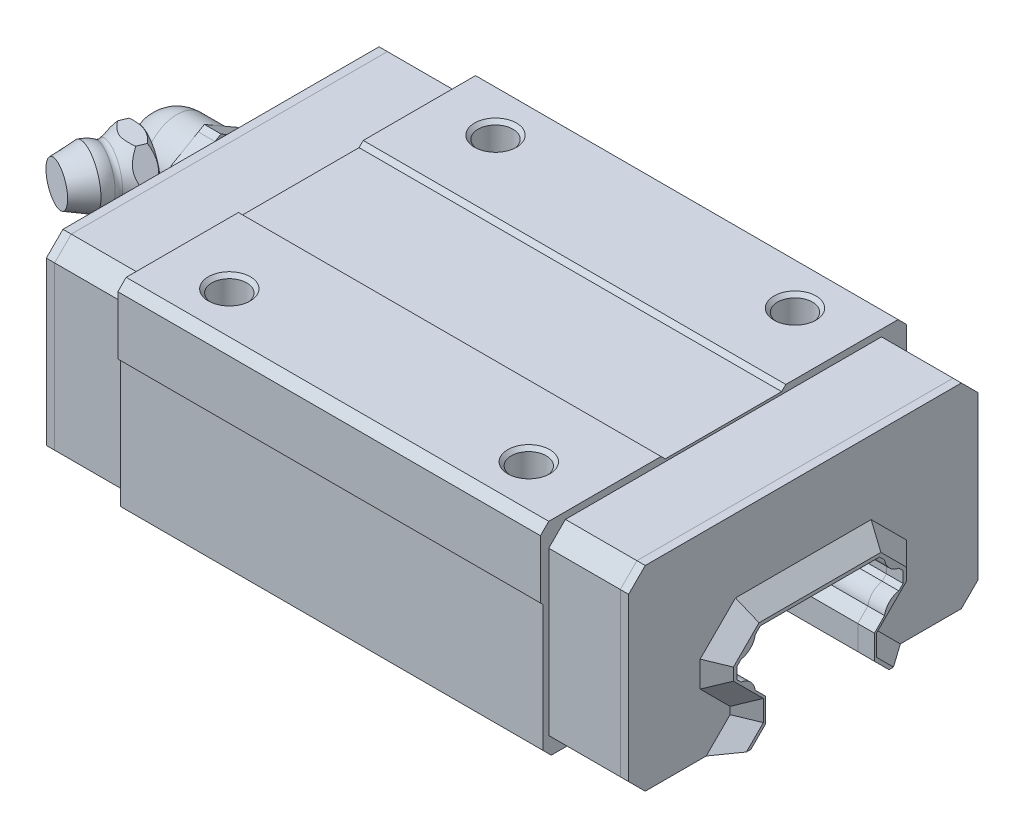
SolidWorks part; units mm, degrees
ref_plane "Front Plane" through (0, 0, 0) normal (0, 0, 1) x (1, 0, 0)
ref_plane "Top Plane" through (0, 0, 0) normal (0, 1, 0) x (1, 0, 0)
ref_plane "Right Plane" through (0, 0, 0) normal (1, 0, 0) x (0, 0, -1)
sketch "Sketch6" plane through (0, 48.7499, 0) normal (0, 1, 0) x (-1, 0, 0)
  line L0 (-67, -46.0009) -> (-233, -46.0009) construction
  line L1 (-124.6001, -68.0009) -> (-124.6001, -24.0009)
  line L2 (-175.4001, -68.0009) -> (-175.4001, -24.0009)
  line L3 (-70, -56.0009) -> (-70, -36.0009)
  line L4 (-116.0002, -67.0009) -> (-116.0002, -25.0009)
  line L5 (-115.0002, -67.0009) -> (-115.0002, -25.0009)
  line L6 (-113.0002, -56.4008) -> (-113.0002, -35.601)
  line L7 (-115.0002, -67.0009) -> (-124.6001, -67.0009)
  line L8 (-113.0002, -56.4008) -> (-115.0002, -58.4008)
  line L9 (-70, -56.0009) -> (-113.0002, -56.0009)
  line L10 (-70, -53.1609) -> (-113.0002, -53.1609)
  line L11 (-113.0002, -35.601) -> (-115.0002, -33.601)
  line L12 (-115.0002, -25.0009) -> (-124.6001, -25.0009)
  line L13 (-70, -38.841) -> (-103.6509, -38.841)
  line L14 (-70, -36.0009) -> (-104.6381, -36.0009)
  line L15 (-230, -56.0009) -> (-230, -36.0009)
  line L16 (-230, -36.0009) -> (-187, -36.0009)
  line L17 (-184, -67.0009) -> (-184, -25.0009)
  line L18 (-185, -67.0009) -> (-185, -25.0009)
  line L19 (-187, -56.4008) -> (-187, -35.601)
  line L20 (-185, -67.0009) -> (-175.4001, -67.0009)
  line L21 (-187, -56.4008) -> (-185, -58.4008)
  line L22 (-230, -56.0009) -> (-187, -56.0009)
  line L23 (-230.0002, -53.1609) -> (-187, -53.1609)
  line L24 (-187, -35.601) -> (-185, -33.601)
  line L25 (-185, -25.0009) -> (-175.4001, -25.0009)
  line L26 (-230.0002, -38.841) -> (-187, -38.841)
  line L27 (-210, -52.0009) -> (-210, -40.0009) construction
  line L28 (-90, -52.0009) -> (-90, -40.0009) construction
  line L29 (-150, -52.0009) -> (-150, -40.0009) construction
  line L30 (-182.2712, -57.0009) -> (-187.2456, -57.0009) construction
  line L31 (-182.2712, -35.0009) -> (-187.2456, -35.0009) construction
  line L32 (-117.7288, -57.0009) -> (-112.7544, -57.0009) construction
  line L33 (-117.7288, -35.0009) -> (-112.7544, -35.0009) construction
  line L34 (-113.0003, -42.0009) -> (-113.0003, -50.0009)
  line L35 (-109.7003, -50.0009) -> (-113.0003, -50.0009)
  line L36 (-111.3204, -42.0009) -> (-113.0003, -42.0009)
  line L37 (-105.7003, -46.0009) -> (-105.7003, -44.3288)
  line L38 (-113.0003, -50.0009) -> (-115.0002, -50.0009)
  line L39 (-113.0003, -42.0009) -> (-115.0002, -42.0009)
  line L40 (-103.483, -36.4794) -> (-107.9177, -34.6425)
  line L41 (-103.6848, -39.3183) -> (-109.7824, -36.7926)
  line L42 (-103.483, -36.4794) -> (-103.6848, -39.3183)
  line L43 (-107.9177, -34.6425) -> (-109.7824, -36.7926)
  line L44 (-104.4235, -43.0391) -> (-104.8382, -44.0402)
  line L45 (-111.8911, -39.946) -> (-112.3058, -40.947)
  line L46 (-105.6176, -44.363) -> (-104.8382, -44.0402)
  line L47 (-106.0608, -41.7115) -> (-106.9334, -43.8181)
  line L48 (-109.7946, -40.1649) -> (-110.6671, -42.2715)
  line L49 (-105.6176, -44.363) -> (-111.9829, -41.7265)
  line L50 (-112.3058, -40.947) -> (-111.9829, -41.7265)
  line L51 (-104.6533, -42.2945) -> (-111.2021, -39.5819)
  line L52 (-110.2333, -38.841) -> (-113.0002, -38.841)
  line L53 (-109.0958, -36.0009) -> (-113.0002, -36.0009)
  line L54 (-124.6001, -53.0009) -> (-175.4001, -53.0009)
  line L55 (-124.6001, -68.0009) -> (-175.4001, -68.0009)
  line L56 (-124.6001, -39.0009) -> (-175.4001, -39.0009)
  line L57 (-124.6001, -24.0009) -> (-175.4001, -24.0009)
  line L58 (-135.5002, -30.0009) -> (-128.5002, -30.0009) construction
  line L59 (-132.0002, -33.5009) -> (-132.0002, -26.5009) construction
  line L60 (-135.5002, -62.0009) -> (-128.5002, -62.0009) construction
  line L61 (-132.0002, -58.5009) -> (-132.0002, -65.5009) construction
  line L62 (-164.4998, -62.0009) -> (-171.4998, -62.0009) construction
  line L63 (-167.9998, -58.5009) -> (-167.9998, -65.5009) construction
  line L64 (-167.9998, -33.5009) -> (-167.9998, -26.5009) construction
  line L65 (-164.4998, -30.0009) -> (-171.4998, -30.0009) construction
  line L66 (-105.0017, -33.8739) -> (-110.025, -46.0009) construction
  circle A0 centre (-210, -46.0009) radius 4.75
  circle A1 centre (-210, -46.0009) radius 3
  circle A2 centre (-90, -46.0009) radius 4.75
  circle A3 centre (-90, -46.0009) radius 3
  arc A4 (-104.5435, -40.5239) -> (-103.6848, -39.3183) centre (-106.7336, -38.0554) ccw
  arc A5 (-109.7824, -36.7926) -> (-110.0277, -38.2523) centre (-106.7336, -38.0555) ccw
  arc A6 (-104.8118, -41.1563) -> (-104.4235, -43.0391) centre (-98.8173, -40.9014) ccw
  arc A7 (-111.8911, -39.946) -> (-110.2851, -38.8892) centre (-114.3437, -34.4701) ccw
  arc A8 (-104.5435, -40.5239) -> (-104.8118, -41.1563) centre (-104.0126, -41.1223) ccw
  arc A9 (-110.2851, -38.8892) -> (-110.0277, -38.2523) centre (-110.8263, -38.3) ccw
  arc A10 (-109.7003, -50.0009) -> (-105.7003, -46.0009) centre (-109.7003, -46.0009) ccw
  circle A11 centre (-132.0002, -30.0009) radius 2.1499
  circle A12 centre (-132.0002, -30.0009) radius 2.5
sketch "Sketch7" plane through (0, 0, 0) normal (0, 0, 1) x (1, 0, 0)
  line L0 (70, 36.7499) -> (113.0002, 36.7499)
  line L1 (70, 22.7499) -> (230, 22.7499)
  line L2 (70, 18.7499) -> (230, 18.7499)
  line L3 (187, 36.7499) -> (230, 36.7499)
  line L4 (124.6001, 48.7499) -> (124.6001, 24.2499)
  line L5 (175.4001, 48.7499) -> (175.4001, 24.2499)
  line L6 (131.6984, 23.4559) -> (131.7153, 24.2498)
  line L7 (128.2851, 24.2498) -> (128.3021, 23.4559)
  line L8 (116.0002, 47.9498) -> (116.0002, 24.2496)
  line L9 (115.0002, 48.3698) -> (115.0002, 24.2496)
  line L10 (113.0002, 37.1498) -> (113.0002, 24.2496)
  line L11 (113.0002, 37.1498) -> (115.0002, 39.1496)
  line L12 (113.0002, 24.2496) -> (187, 24.2496)
  line L13 (101.8003, 43.7494) -> (117.729, 43.7494) construction
  line L14 (113.0005, 39.6295) -> (113.0005, 47.8695)
  line L15 (110.0005, 47.7494) -> (113.0005, 47.7494)
  line L16 (115.0002, 48.3698) -> (113.5002, 48.3695)
  line L17 (115.0002, 46.0594) -> (113.0005, 46.0594)
  line L18 (115.0002, 39.1295) -> (113.5002, 39.1295)
  line L19 (115.0002, 41.4396) -> (113.0005, 41.4396)
  line L20 (113.5002, 39.1295) -> (113.0005, 39.6295)
  line L21 (113.0005, 47.8695) -> (113.5002, 48.3695)
  line L22 (111.1003, 40.2494) -> (105.9004, 40.2494)
  line L23 (111.1003, 40.2096) -> (111.1003, 40.2494)
  line L24 (112.6004, 43.7496) -> (111.1003, 40.2494)
  line L25 (111.7006, 43.7494) -> (110.1005, 40.2494)
  line L26 (105.9004, 40.2494) -> (105.5003, 40.8294)
  line L27 (105.9, 47.2496) -> (105.5, 46.6696)
  line L28 (111.1003, 47.2494) -> (105.9, 47.2496)
  line L29 (111.7006, 43.7494) -> (110.1003, 47.2495)
  line L30 (112.6004, 43.7496) -> (111.1003, 47.2494)
  line L31 (110.0005, 39.7494) -> (113.0005, 39.7494)
  line L32 (111.1003, 40.2096) -> (111.1003, 40.2494)
  line L33 (114.6187, 41.5681) -> (115.0003, 41.5347)
  line L34 (114.6185, 45.931) -> (115.0003, 45.9644)
  line L35 (184, 24.2496) -> (184, 47.9498)
  line L36 (185, 24.2496) -> (185, 47.9498)
  line L37 (187, 24.2496) -> (187, 37.1498)
  line L38 (185.0002, 39.1495) -> (187, 37.1498)
  line L39 (175.4001, 47.9498) -> (185, 47.9498)
  line L40 (182.2712, 43.7494) -> (187.2456, 43.7494) construction
  line L41 (115.0002, 47.9498) -> (124.6001, 47.9498)
  line L42 (130.0003, 25.5223) -> (130.0003, 21.4961) construction
  line L43 (170, 25.5222) -> (170, 21.496) construction
  line L44 (210, 38.7499) -> (210, 16.521) construction
  line L45 (70, 36.7499) -> (70, 18.7499)
  line L46 (230, 36.7499) -> (230, 18.7499)
  line L47 (94.75, 36.7499) -> (94.75, 28.2499) construction
  line L48 (85.25, 28.2499) -> (94.75, 28.2499) construction
  line L49 (93, 28.2499) -> (93, 18.7499) construction
  line L50 (87, 28.2499) -> (87, 18.7499) construction
  line L51 (85.25, 36.7499) -> (85.25, 28.2499) construction
  line L52 (90, 38.7499) -> (90, 16.521) construction
  line L53 (150, 38.7499) -> (150, 16.521) construction
  line L54 (70, 33.9098) -> (113.0002, 33.9098)
  line L55 (70, 32.5797) -> (113.0002, 32.5797)
  line L56 (187, 33.9098) -> (230, 33.9098)
  line L57 (187, 32.5797) -> (230, 32.5797)
  line L58 (124.6001, 48.7499) -> (175.4001, 48.7499)
  line L59 (124.6001, 40.7497) -> (175.4001, 40.7497)
  line L60 (132.0002, 39.8278) -> (132.0002, 50.2497) construction
  line L61 (168, 39.8278) -> (168, 50.2497) construction
  line L62 (70, 30.3455) -> (113.0002, 30.3455)
  line L63 (187, 30.3455) -> (230, 30.3455)
  arc A0 (128.7304, 22.9325) -> (131.2696, 22.9325) centre (130, 27.2497) ccw
  arc A1 (128.3021, 23.4559) -> (128.7304, 22.9325) centre (128.8998, 23.5081) ccw
  arc A2 (131.2696, 22.9325) -> (131.6984, 23.4559) centre (131.1007, 23.5082) ccw
  arc A3 (110.0005, 47.7494) -> (108.0921, 47.2653) centre (109.9996, 43.7494) ccw
  arc A4 (108.1005, 40.2499) -> (110.0005, 39.7674) centre (110.0005, 43.7499) ccw
  arc A5 (113.9171, 45.3473) -> (113.9171, 42.152) centre (119.7004, 43.7496) ccw
  arc A6 (114.6185, 45.931) -> (113.9171, 45.3473) centre (114.6881, 45.134) ccw
  arc A7 (113.9171, 42.152) -> (114.6187, 41.5681) centre (114.6882, 42.3651) ccw
  arc A8 (105.7008, 46.2499) -> (104.7887, 46.0449) centre (105.7035, 44.1063) ccw
  arc A9 (104.7887, 46.0449) -> (104.0413, 45.4809) centre (105.7763, 43.9588) ccw
  arc A10 (104.0413, 45.4809) -> (103.5635, 44.6741) centre (105.9462, 43.8081) ccw
  arc A11 (103.5635, 44.6741) -> (103.4004, 43.7502) centre (106.0925, 43.7513) ccw
  arc A12 (103.4004, 43.7502) -> (103.5629, 42.8265) centre (106.092, 43.7475) ccw
  arc A13 (103.5629, 42.8265) -> (104.04, 42.0196) centre (105.9452, 43.6906) ccw
  arc A14 (104.04, 42.0196) -> (104.7881, 41.4548) centre (105.7751, 43.5399) ccw
  arc A15 (104.7881, 41.4548) -> (105.7007, 41.2499) centre (105.7025, 43.3929) ccw
  arc A16 (105.7007, 41.2499) -> (106.6128, 41.4552) centre (105.6973, 43.3935) ccw
  arc A17 (106.6128, 41.4552) -> (107.36, 42.0194) centre (105.6245, 43.5411) ccw
  arc A18 (107.36, 42.0194) -> (107.8376, 42.8263) centre (105.4545, 43.6918) ccw
  arc A19 (107.8376, 42.8263) -> (108.0004, 43.7502) centre (105.3084, 43.7485) ccw
  arc A20 (108.0004, 43.7502) -> (107.8378, 44.6738) centre (105.3089, 43.7523) ccw
  arc A21 (107.8378, 44.6738) -> (107.3605, 45.4806) centre (105.4558, 43.8092) ccw
  arc A22 (107.3605, 45.4806) -> (106.6122, 46.0453) centre (105.6259, 43.96) ccw
  arc A23 (106.6122, 46.0453) -> (105.6997, 46.2499) centre (105.6983, 44.1069) ccw
  arc A24 (104.5765, 41.5688) -> (105.2727, 40.9529) centre (106.9306, 43.5287) ccw
  arc A25 (105.2727, 40.9529) -> (106.1252, 40.5833) centre (106.8262, 43.3679) ccw
  arc A26 (106.1252, 40.5833) -> (107.0502, 40.5112) centre (106.8005, 43.2757) ccw
  arc A27 (107.0502, 40.5112) -> (107.9468, 40.7465) centre (106.7945, 43.3114) ccw
  arc A28 (107.9468, 40.7465) -> (108.7234, 41.2552) centre (106.7298, 43.4512) ccw
  arc A29 (108.7234, 41.2552) -> (109.3127, 41.9734) centre (106.5851, 43.6108) ccw
  arc A30 (109.3127, 41.9734) -> (109.6775, 42.8287) centre (106.4133, 43.7155) ccw
  arc A31 (109.6775, 42.8287) -> (109.8005, 43.7499) centre (106.2983, 43.7488) ccw
  arc A32 (109.8005, 43.7499) -> (109.6773, 44.6717) centre (106.2983, 43.7509) ccw
  arc A33 (109.6773, 44.6717) -> (109.3127, 45.5264) centre (106.4134, 43.7843) ccw
  arc A34 (109.3127, 45.5264) -> (108.7231, 46.2448) centre (106.5851, 43.889) ccw
  arc A35 (108.7231, 46.2448) -> (107.9455, 46.7539) centre (106.7299, 44.0488) ccw
  arc A36 (107.9455, 46.7539) -> (107.047, 46.9889) centre (106.7945, 44.1886) ccw
  arc A37 (107.047, 46.9889) -> (106.1224, 46.9158) centre (106.8005, 44.2239) ccw
  arc A38 (106.1224, 46.9158) -> (105.2712, 46.5459) centre (106.8263, 44.1315) ccw
  arc A39 (105.2712, 46.5459) -> (104.5758, 45.9302) centre (106.9308, 43.9708) ccw
sketch "Sketch8" plane through (46.0009, 0, 0) normal (-1, 0, 0) x (0, 0, 1)
  line L0 (-37.0009, 19.5499) -> (-43.0009, 19.5499)
  line L1 (-39.4509, 29.9298) -> (-39.4509, 26.9999)
  line L2 (-52.5507, 29.9298) -> (-52.5507, 26.9999)
  line L3 (-39.4509, 26.9999) -> (-37.7009, 25.2499)
  line L4 (-59.4009, 25.2498) -> (-54.3007, 25.2499)
  line L5 (-56.0005, 20.5496) -> (-55.0004, 19.5496)
  line L6 (-36.0005, 20.5495) -> (-37.0009, 19.5499)
  line L7 (-56.0006, 23.5496) -> (-56.0005, 20.5496)
  line L8 (-36.0006, 23.5497) -> (-36.0005, 20.5495)
  line L9 (-48.5009, 20.0499) -> (-43.5009, 20.0499)
  line L10 (-49.0007, 19.5499) -> (-48.5009, 20.0499)
  line L11 (-43.5009, 20.0499) -> (-43.0009, 19.5499)
  line L12 (-49.0007, 19.5499) -> (-55.0004, 19.5496)
  line L13 (-62.0009, 25.2499) -> (-62.0009, 25.0499)
  line L14 (-30.0009, 25.0499) -> (-30.0009, 25.2499)
  line L15 (-25.0005, 27.2496) -> (-27.0005, 25.2496)
  line L16 (-37.7009, 25.2499) -> (-34.3325, 25.2499)
  line L17 (-37.2009, 28.9813) -> (-37.2009, 28.1183)
  line L18 (-37.2009, 28.1183) -> (-34.3325, 25.2499)
  line L19 (-57.7024, 24.256) -> (-57.6679, 25.2496)
  line L20 (-61.1328, 25.2497) -> (-61.0984, 24.2561)
  line L21 (-65.0005, 25.2497) -> (-67.0005, 27.2496)
  line L22 (-65.0005, 25.2497) -> (-62.0009, 25.2497)
  line L23 (-54.8007, 28.1183) -> (-54.8007, 28.9813)
  line L24 (-57.669, 25.2497) -> (-54.8007, 28.1183)
  line L25 (-59.4009, 26.7499) -> (-59.4009, 22.65) construction
  line L26 (-32.601, 26.7499) -> (-32.601, 22.65) construction
  line L27 (-50.7509, 29.0499) -> (-41.2509, 29.0499) construction
  line L28 (-43.0009, 29.0499) -> (-43.0009, 19.5499) construction
  line L29 (-49.0009, 29.0499) -> (-49.0007, 19.5499) construction
  line L30 (-46.0009, 51.5499) -> (-46.0009, 17.5499) construction
  line L31 (-36.0009, 34.7098) -> (-36.0009, 33.3798)
  line L32 (-38.8405, 37.5495) -> (-38.2327, 36.9417)
  line L33 (-56.0009, 34.7098) -> (-56.0009, 33.3798)
  line L34 (-39.4509, 29.9298) -> (-38.2345, 31.1456)
  line L35 (-53.1609, 37.5499) -> (-38.8405, 37.5495)
  line L36 (-56.0009, 33.3798) -> (-55.485, 32.8641)
  line L37 (-56.0009, 34.7098) -> (-55.473, 35.2369)
  line L38 (-53.7666, 31.1457) -> (-52.5507, 29.9298)
  line L39 (-45.2756, 48.7499) -> (-27.0008, 48.7499)
  line L40 (-53.7684, 36.9415) -> (-53.1609, 37.5499)
  line L41 (-36.5281, 35.2371) -> (-36.0009, 34.7098)
  line L42 (-36.5161, 32.864) -> (-36.0009, 33.3798)
  line L43 (-51.0009, 44.5499) -> (-32.0041, 44.5499) construction
  line L44 (-46.0013, 49.1689) -> (-44.0631, 48.0499)
  line L45 (-50.7509, 37.5499) -> (-50.7509, 29.0499) construction
  line L46 (-41.2509, 37.5499) -> (-41.2509, 29.0499) construction
  line L47 (-35.0009, 47.5497) -> (-35.0009, 41.5497) construction
  line L48 (-60.0009, 44.5497) -> (-54.0009, 44.5497) construction
  line L49 (-54.1543, 39.9498) -> (-37.8474, 39.9498)
  line L50 (-37.8474, 39.9498) -> (-33.6005, 35.7029)
  line L51 (-65.0011, 48.7499) -> (-46.726, 48.7499)
  line L52 (-50.0009, 46.8597) -> (-50.0009, 42.2404)
  line L53 (-50.0009, 46.8597) -> (-46.0013, 49.1689)
  line L54 (-25.0009, 46.7499) -> (-25.0005, 27.2496)
  line L55 (-27.0008, 48.7499) -> (-25.0009, 46.7499)
  line L56 (-50.0009, 42.2404) -> (-46.0004, 39.9307)
  line L57 (-33.6005, 35.7029) -> (-33.6008, 32.5814)
  line L58 (-37.2009, 28.9813) -> (-33.6008, 32.5814)
  line L59 (-67.0005, 27.2496) -> (-67.0009, 46.75)
  line L60 (-58.4008, 32.5814) -> (-58.4008, 35.7033)
  line L61 (-58.4008, 32.5814) -> (-54.8007, 28.9813)
  line L62 (-65.0011, 48.7499) -> (-67.0009, 46.75)
  line L63 (-57.0009, 41.5497) -> (-57.0009, 47.5497) construction
  line L64 (-58.4008, 35.7033) -> (-54.1543, 39.9498)
  line L65 (-46.0004, 39.9307) -> (-44.0528, 41.05)
  line L66 (-38.2342, 41.3038) -> (-35.4801, 42.0495)
  line L67 (-40.0506, 41.5197) -> (-40.1406, 41.0497)
  line L68 (-42.5604, 44.5498) -> (-41.9104, 41.0498)
  line L69 (-44.8706, 44.5494) -> (-44.2206, 41.0492)
  line L70 (-44.2206, 41.0492) -> (-40.1406, 41.0497)
  line L71 (-38.2508, 47.7997) -> (-35.4807, 47.0497)
  line L72 (-40.0504, 47.5696) -> (-40.1404, 48.0495)
  line L73 (-42.5604, 44.5498) -> (-41.9104, 48.0496)
  line L74 (-44.8706, 44.5494) -> (-44.2208, 48.0497)
  line L75 (-44.2208, 48.0497) -> (-40.1404, 48.0495)
  line L76 (-68.0009, 48.5497) -> (-68.0009, 41.5499)
  line L77 (-67.7009, 41.2501) -> (-67.7009, 26.0526)
  line L78 (-67.6988, 41.2507) -> (-67.9988, 41.5508)
  line L79 (-66.9983, 49.5493) -> (-67.9984, 48.5492)
  line L80 (-67.0009, 49.5499) -> (-53.5007, 49.5499)
  line L81 (-64.1508, 49.5499) -> (-64.1508, 42.5499) construction
  line L82 (-64.5009, 49.5499) -> (-64.5009, 43.5499) construction
  line L83 (-64.5009, 43.5499) -> (-59.5009, 43.5499) construction
  line L84 (-64.1508, 42.5499) -> (-59.8508, 42.5499) construction
  line L85 (-64.1497, 42.55) -> (-61.9996, 41.3087) construction
  line L86 (-59.8488, 42.5498) -> (-61.9996, 41.3087) construction
  line L87 (-62.0009, 51.0499) -> (-62.0009, 40.6281) construction
  line L88 (-59.5009, 49.5499) -> (-59.5009, 43.5499) construction
  line L89 (-59.8508, 49.5499) -> (-59.8508, 42.5499) construction
  line L90 (-59.5009, 43.5499) -> (-59.8501, 42.9434) construction
  line L91 (-64.4989, 43.5499) -> (-64.1489, 42.9437) construction
  line L92 (-67.6988, 26.0505) -> (-66.6987, 25.0504)
  line L93 (-66.7009, 25.0499) -> (-62.0009, 25.0499)
  line L94 (-30.0009, 25.0499) -> (-25.3007, 25.0499)
  line L95 (-24.2991, 26.0506) -> (-25.2991, 25.0505)
  line L96 (-24.3007, 41.2501) -> (-24.3007, 26.0499)
  line L97 (-24.0009, 48.5497) -> (-24.0009, 41.5499)
  line L98 (-24.2991, 41.2507) -> (-23.9991, 41.5507)
  line L99 (-24.9997, 49.5495) -> (-23.9996, 48.5494)
  line L100 (-38.5009, 49.5499) -> (-25.0009, 49.5499)
  line L101 (-53.0009, 49.0499) -> (-46.2075, 49.0499)
  line L102 (-52.9991, 49.0506) -> (-53.499, 49.5505)
  line L103 (-45.7951, 49.0499) -> (-39.0009, 49.0499)
  line L104 (-38.9989, 49.0505) -> (-38.4989, 49.5504)
  line L105 (-30.0009, 51.0499) -> (-30.0009, 40.6281) construction
  line L106 (-45.2756, 48.7499) -> (-46.726, 48.7499)
  line L107 (-45.7951, 49.0499) -> (-46.2075, 49.0499)
  line L108 (-54.3007, 25.2499) -> (-52.5507, 26.9999)
  line L109 (-37.7009, 25.2499) -> (-39.4509, 26.9999)
  line L110 (-30.0009, 25.2499) -> (-27.0005, 25.2496)
  line L111 (-30.0009, 25.2497) -> (-27.0005, 25.2496)
  line L112 (-30.0009, 25.2497) -> (-34.3325, 25.2499)
  line L113 (-62.0009, 25.2497) -> (-61.1328, 25.2497)
  line L114 (-59.4009, 25.2498) -> (-61.1328, 25.2497)
  line L115 (-56.0006, 23.5496) -> (-54.3007, 25.2499)
  line L116 (-37.7009, 25.2499) -> (-36.0006, 23.5497)
  arc A0 (-60.6705, 23.7327) -> (-58.1313, 23.7327) centre (-59.4009, 28.0499) ccw
  arc A1 (-61.0984, 24.2561) -> (-60.6705, 23.7327) centre (-60.5007, 24.3082) ccw
  arc A2 (-58.1313, 23.7327) -> (-57.7024, 24.256) centre (-58.3001, 24.3085) ccw
  arc A3 (-55.473, 35.2369) -> (-53.7684, 36.9415) centre (-55.8019, 37.2705) ccw
  arc A4 (-36.5161, 32.864) -> (-38.2345, 31.1456) centre (-36.199, 30.8285) ccw
  arc A5 (-53.7666, 31.1457) -> (-55.485, 32.8641) centre (-55.8021, 30.8286) ccw
  arc A6 (-38.2327, 36.9417) -> (-36.5281, 35.2371) centre (-36.1991, 37.2707) ccw
  arc A7 (-44.0684, 48.0497) -> (-44.0684, 41.0497) centre (-46.0009, 44.5497) ccw
  arc A8 (-38.2508, 47.7997) -> (-39.1823, 47.4008) centre (-38.3908, 46.8397) ccw
  arc A9 (-48.0009, 41.0856) -> (-47.9374, 41.0497) centre (-46.0009, 44.5497) ccw
  arc A10 (-39.1808, 41.6999) -> (-40.3645, 41.2349) centre (-39.3808, 40.4699) ccw
  arc A11 (-39.1808, 41.6999) -> (-38.2511, 41.3017) centre (-38.3909, 42.2599) ccw
  arc A12 (-53.7422, 30.8287) -> (-53.7423, 30.8413) centre (-55.8022, 30.8287) ccw
  arc A13 (-35.0661, 42.3006) -> (-35.0661, 46.7987) centre (-35.0009, 44.5497) ccw
  circle A14 centre (-57.0009, 44.5497) radius 2.25
  arc A15 (-40.3708, 47.8598) -> (-39.1795, 47.3918) centre (-39.3808, 48.6298) ccw
  arc A16 (-38.2508, 47.7997) -> (-38.6658, 47.6155) centre (-38.2229, 47.1773) ccw
  arc A17 (-38.6658, 47.6155) -> (-38.9472, 47.2488) centre (-37.6054, 46.5103) ccw
  arc A18 (-38.9472, 47.2488) -> (-39.1426, 46.8273) centre (-36.3787, 45.8019) ccw
  arc A19 (-39.1426, 46.8273) -> (-39.2828, 46.384) centre (-34.9363, 45.2534) ccw
  arc A20 (-39.2828, 46.384) -> (-39.3827, 45.9292) centre (-33.5437, 44.8846) ccw
  arc A21 (-39.3827, 45.9292) -> (-39.45, 45.4683) centre (-32.3728, 44.6714) ccw
  arc A22 (-39.45, 45.4683) -> (-39.4887, 45.004) centre (-31.5386, 44.5752) ccw
  arc A23 (-39.4887, 45.004) -> (-39.5009, 44.5383) centre (-31.1105, 44.5503) ccw
  arc A24 (-39.5009, 44.5383) -> (-39.4875, 44.074) centre (-31.121, 44.5488) ccw
  arc A25 (-39.4875, 44.074) -> (-39.4476, 43.6103) centre (-31.568, 44.5218) ccw
  arc A26 (-39.4476, 43.6103) -> (-39.3788, 43.1484) centre (-32.4201, 44.421) ccw
  arc A27 (-39.3788, 43.1484) -> (-39.2771, 42.6938) centre (-33.6062, 44.201) ccw
  arc A28 (-39.2771, 42.6938) -> (-39.1344, 42.2504) centre (-35.0079, 43.8233) ccw
  arc A29 (-39.1344, 42.2504) -> (-38.9349, 41.8294) centre (-36.4501, 43.2643) ccw
  arc A30 (-38.9349, 41.8294) -> (-38.6456, 41.4659) centre (-37.6601, 42.5472) ccw
  arc A31 (-38.6456, 41.4659) -> (-38.2231, 41.3005) centre (-38.2334, 41.8964) ccw
  arc A32 (-35.4807, 47.0497) -> (-36.0107, 46.6248) centre (-35.3565, 46.3517) ccw
  arc A33 (-36.0107, 46.6248) -> (-36.2648, 45.9619) centre (-33.5257, 45.2921) ccw
  arc A34 (-36.2648, 45.9619) -> (-36.3916, 45.2619) centre (-31.3605, 44.7126) ccw
  arc A35 (-36.3916, 45.2619) -> (-36.4309, 44.5497) centre (-30.0542, 44.5544) ccw
  arc A36 (-36.4309, 44.5497) -> (-36.3918, 43.8395) centre (-30.0528, 44.545) ccw
  arc A37 (-36.3918, 43.8395) -> (-36.2653, 43.1393) centre (-31.3554, 44.3877) ccw
  arc A38 (-36.2653, 43.1393) -> (-36.0113, 42.4755) centre (-33.5214, 43.8089) ccw
  arc A39 (-36.0113, 42.4755) -> (-35.4809, 42.0497) centre (-35.3563, 42.7481) ccw
  arc A40 (-35.4809, 42.0497) -> (-34.9511, 42.4746) centre (-35.6052, 42.7474) ccw
  arc A41 (-34.9511, 42.4746) -> (-34.697, 43.1375) centre (-37.4361, 43.8073) ccw
  arc A42 (-34.697, 43.1375) -> (-34.5703, 43.8375) centre (-39.6014, 44.3868) ccw
  arc A43 (-34.5703, 43.8375) -> (-34.5309, 44.5497) centre (-40.9077, 44.545) ccw
  arc A44 (-34.5309, 44.5497) -> (-34.5701, 45.2598) centre (-40.909, 44.5544) ccw
  arc A45 (-34.5701, 45.2598) -> (-34.6966, 45.9601) centre (-39.6064, 44.7117) ccw
  arc A46 (-34.6966, 45.9601) -> (-34.9506, 46.6239) centre (-37.4405, 45.2904) ccw
  arc A47 (-34.9506, 46.6239) -> (-35.4807, 47.0497) centre (-35.6055, 46.3515) ccw
extrude "Boss-Extrude1" add sketch "Sketch8" against normal up to vertex (137.9991 mm away) from vertex at -69.9993 starting at point (116.0002, 48.7499, -25.0009)
ref_plane "Plane2" through (46.0009, 0, 0) normal (-1, 0, 0) x (0, 0, 1)
sketch "Sketch9" plane through (46.0009, 0, 0) normal (-1, 0, 0) x (0, 0, 1)
  line L0 (-67.0009, 49.5499) -> (-53.5007, 49.5499) construction
  line L2 (-66.6987, 25.0504) -> (-62.0009, 25.0499)
  line L3 (-66.6987, 25.0504) -> (-67.7009, 26.0526)
  line L4 (-68.0009, 48.5497) -> (-68.0009, 41.5499) construction
  line L5 (-67.7009, 26.0526) -> (-67.6988, 41.2507)
  line L8 (-68.0009, 41.5499) -> (-67.6988, 41.2507)
  line L11 (-68.0009, 48.5497) -> (-67.0009, 49.5499)
  line L12 (-62.0009, 25.2499) -> (-62.0009, 25.0499) construction
  line L13 (-24.2991, 26.0506) -> (-25.2991, 25.0505) construction
  line L14 (-30.0009, 25.0499) -> (-25.3007, 25.0499) construction
  line L15 (-53.5007, 49.5499) -> (-53.4984, 49.5499)
  line L17 (-30.0009, 25.0499) -> (-30.0009, 25.2499) construction
  line L19 (-24.3007, 41.2501) -> (-24.3007, 26.0499) construction
  line L20 (-24.0009, 48.5497) -> (-24.0009, 41.5499) construction
  line L21 (-24.2991, 41.2507) -> (-23.9991, 41.5507) construction
  line L23 (-24.9997, 49.5495) -> (-23.9996, 48.5494) construction
  line L24 (-38.5009, 49.5499) -> (-25.0009, 49.5499) construction
  line L26 (-38.9989, 49.0505) -> (-38.4989, 49.5504) construction
  line L27 (-45.7951, 49.0499) -> (-39.0009, 49.0499) construction
  line L29 (-45.7951, 49.0499) -> (-46.2075, 49.0499) construction
  line L30 (-53.0009, 49.0499) -> (-46.2075, 49.0499) construction
  line L31 (-52.9991, 49.0506) -> (-53.499, 49.5505) construction
  line L32 (-67.0009, 49.5499) -> (-53.5007, 49.5499)
  line L36 (-68.0009, 48.5497) -> (-68.0009, 41.5499)
  line L44 (-62.0009, 25.2499) -> (-62.0009, 25.0499)
  line L45 (-24.3007, 26.0489) -> (-25.2997, 25.0499)
  line L46 (-30.0009, 25.0499) -> (-25.2997, 25.0499)
  line L49 (-30.0009, 25.0499) -> (-30.0009, 44.6635)
  line L51 (-24.3007, 41.249) -> (-24.3007, 26.0489)
  line L52 (-24.0009, 48.5508) -> (-24.0009, 41.5488)
  line L53 (-24.3007, 41.249) -> (-24.0009, 41.5488)
  line L55 (-25.0001, 49.5499) -> (-24.0009, 48.5508)
  line L56 (-38.4994, 49.5499) -> (-25.0001, 49.5499)
  line L58 (-38.9994, 49.0499) -> (-38.4994, 49.5499)
  line L59 (-45.7951, 49.0499) -> (-38.9994, 49.0499)
  line L61 (-45.7951, 49.0499) -> (-46.2075, 49.0499)
  line L62 (-52.9984, 49.0499) -> (-46.2075, 49.0499)
  line L63 (-52.9984, 49.0499) -> (-53.4984, 49.5499)
  line L64 (-30.0009, 25.0499) -> (-30.0009, 44.6635)
  line L66 (-30.0009, 44.6635) -> (-62.0009, 44.6635)
  line L67 (-62.0009, 25.0499) -> (-62.0009, 44.6635)
extrude "Boss-Extrude4" add sketch "Sketch9" against normal up to vertex (129.3992 mm away) from vertex at -78.5992 contours L44 L67 L66 L49 L46 L45 L51 L53 L52 L55 L56 L58 L59 L61 L62 L63 L15 L32 L11 L36 L8 L5 L3 L2 starting at point (124.6001, 48.7499, -68.0009)
sketch "Sketch11" plane through (184, 0, 0) normal (1, 0, 0) x (0, 0, -1)
  line L25 (37.8474, 39.9498) -> (54.1543, 39.9498)
  line L26 (54.1543, 39.9498) -> (58.4008, 35.7033)
  line L27 (58.4008, 35.7033) -> (58.4008, 32.5814)
  line L28 (58.4008, 32.5814) -> (54.8007, 28.9813)
  line L29 (54.8007, 28.9813) -> (54.8007, 28.1183)
  line L30 (54.8007, 28.1183) -> (57.6689, 25.2498)
  line L31 (57.6689, 25.2498) -> (59.4009, 25.2498)
  line L32 (59.4009, 25.2498) -> (61.1328, 25.2497)
  line L33 (61.1328, 25.2497) -> (62.0009, 25.2497)
  line L34 (62.0009, 25.2497) -> (65.0005, 25.2497)
  line L35 (65.0005, 25.2497) -> (67.0005, 27.2496)
  line L36 (67.0005, 27.2496) -> (67.0009, 46.75)
  line L37 (67.0009, 46.75) -> (65.0011, 48.7499)
  line L38 (65.0011, 48.7499) -> (27.0008, 48.7499)
  line L39 (27.0008, 48.7499) -> (25.0009, 46.7499)
  line L40 (25.0009, 46.7499) -> (25.0005, 27.2496)
  line L41 (25.0005, 27.2496) -> (27.0005, 25.2496)
  line L42 (27.0005, 25.2496) -> (30.0009, 25.2499)
  line L43 (30.0009, 25.2499) -> (30.0009, 25.2497)
  line L44 (30.0009, 25.2497) -> (34.3325, 25.2499)
  line L45 (34.3325, 25.2499) -> (37.2009, 28.1183)
  line L46 (37.2009, 28.1183) -> (37.2009, 28.9813)
  line L47 (37.2009, 28.9813) -> (33.6008, 32.5814)
  line L48 (33.6008, 32.5814) -> (33.6005, 35.7029)
  line L49 (33.6005, 35.7029) -> (37.8474, 39.9498)
  line L50 (37.8474, 39.9498) -> (54.1543, 39.9498)
  line L51 (54.1543, 39.9498) -> (58.4008, 35.7033)
  line L52 (58.4008, 35.7033) -> (58.4008, 32.5814)
  line L53 (58.4008, 32.5814) -> (54.8007, 28.9813)
  line L54 (54.8007, 28.9813) -> (54.8007, 28.1183)
  line L55 (54.8007, 28.1183) -> (57.6689, 25.2498)
  line L56 (57.6689, 25.2498) -> (59.4009, 25.2498)
  line L57 (59.4009, 25.2498) -> (61.1328, 25.2497)
  line L58 (61.1328, 25.2497) -> (62.0009, 25.2497)
  line L59 (62.0009, 25.2497) -> (65.0005, 25.2497)
  line L60 (65.0005, 25.2497) -> (67.0005, 27.2496)
  line L61 (67.0005, 27.2496) -> (67.0009, 46.75)
  line L62 (67.0009, 46.75) -> (65.0011, 48.7499)
  line L63 (65.0011, 48.7499) -> (27.0008, 48.7499)
  line L64 (27.0008, 48.7499) -> (25.0009, 46.7499)
  line L65 (25.0009, 46.7499) -> (25.0005, 27.2496)
  line L66 (25.0005, 27.2496) -> (27.0005, 25.2496)
  line L67 (27.0005, 25.2496) -> (30.0009, 25.2499)
  line L68 (30.0009, 25.2499) -> (30.0009, 25.2497)
  line L69 (30.0009, 25.2497) -> (34.3325, 25.2499)
  line L70 (34.3325, 25.2499) -> (37.2009, 28.1183)
  line L71 (37.2009, 28.1183) -> (37.2009, 28.9813)
  line L72 (37.2009, 28.9813) -> (33.6008, 32.5814)
  line L73 (33.6008, 32.5814) -> (33.6005, 35.7029)
  line L74 (33.6005, 35.7029) -> (37.8474, 39.9498)
  dimension "D1" = 0
extrude "Boss-Extrude5" add sketch "Sketch11" along normal up to vertex (1 mm away) separate body up to point (185, 48.7499, -25.0009)
sketch "Sketch12" plane through (116.0002, 0, 0) normal (-1, 0, 0) x (0, 0, 1)
  line L25 (-54.1543, 39.9498) -> (-37.8474, 39.9498)
  line L26 (-37.8474, 39.9498) -> (-33.6005, 35.7029)
  line L27 (-33.6005, 35.7029) -> (-33.6008, 32.5814)
  line L28 (-33.6008, 32.5814) -> (-37.2009, 28.9813)
  line L29 (-37.2009, 28.9813) -> (-37.2009, 28.1183)
  line L30 (-37.2009, 28.1183) -> (-34.3325, 25.2499)
  line L31 (-34.3325, 25.2499) -> (-30.0009, 25.2497)
  line L32 (-30.0009, 25.2497) -> (-30.0009, 25.2499)
  line L33 (-30.0009, 25.2499) -> (-27.0005, 25.2496)
  line L34 (-27.0005, 25.2496) -> (-25.0005, 27.2496)
  line L35 (-25.0005, 27.2496) -> (-25.0009, 46.7499)
  line L36 (-25.0009, 46.7499) -> (-27.0008, 48.7499)
  line L37 (-27.0008, 48.7499) -> (-65.0011, 48.7499)
  line L38 (-65.0011, 48.7499) -> (-67.0009, 46.75)
  line L39 (-67.0009, 46.75) -> (-67.0005, 27.2496)
  line L40 (-67.0005, 27.2496) -> (-65.0005, 25.2497)
  line L41 (-65.0005, 25.2497) -> (-62.0009, 25.2497)
  line L42 (-62.0009, 25.2497) -> (-61.1328, 25.2497)
  line L43 (-61.1328, 25.2497) -> (-59.4009, 25.2498)
  line L44 (-59.4009, 25.2498) -> (-57.6689, 25.2498)
  line L45 (-57.6689, 25.2498) -> (-54.8007, 28.1183)
  line L46 (-54.8007, 28.1183) -> (-54.8007, 28.9813)
  line L47 (-54.8007, 28.9813) -> (-58.4008, 32.5814)
  line L48 (-58.4008, 32.5814) -> (-58.4008, 35.7033)
  line L49 (-58.4008, 35.7033) -> (-54.1543, 39.9498)
  line L50 (-54.1543, 39.9498) -> (-37.8474, 39.9498)
  line L51 (-37.8474, 39.9498) -> (-33.6005, 35.7029)
  line L52 (-33.6005, 35.7029) -> (-33.6008, 32.5814)
  line L53 (-33.6008, 32.5814) -> (-37.2009, 28.9813)
  line L54 (-37.2009, 28.9813) -> (-37.2009, 28.1183)
  line L55 (-37.2009, 28.1183) -> (-34.3325, 25.2499)
  line L56 (-34.3325, 25.2499) -> (-30.0009, 25.2497)
  line L57 (-30.0009, 25.2497) -> (-30.0009, 25.2499)
  line L58 (-30.0009, 25.2499) -> (-27.0005, 25.2496)
  line L59 (-27.0005, 25.2496) -> (-25.0005, 27.2496)
  line L60 (-25.0005, 27.2496) -> (-25.0009, 46.7499)
  line L61 (-25.0009, 46.7499) -> (-27.0008, 48.7499)
  line L62 (-27.0008, 48.7499) -> (-65.0011, 48.7499)
  line L63 (-65.0011, 48.7499) -> (-67.0009, 46.75)
  line L64 (-67.0009, 46.75) -> (-67.0005, 27.2496)
  line L65 (-67.0005, 27.2496) -> (-65.0005, 25.2497)
  line L66 (-65.0005, 25.2497) -> (-62.0009, 25.2497)
  line L67 (-62.0009, 25.2497) -> (-61.1328, 25.2497)
  line L68 (-61.1328, 25.2497) -> (-59.4009, 25.2498)
  line L69 (-59.4009, 25.2498) -> (-57.6689, 25.2498)
  line L70 (-57.6689, 25.2498) -> (-54.8007, 28.1183)
  line L71 (-54.8007, 28.1183) -> (-54.8007, 28.9813)
  line L72 (-54.8007, 28.9813) -> (-58.4008, 32.5814)
  line L73 (-58.4008, 32.5814) -> (-58.4008, 35.7033)
  line L74 (-58.4008, 35.7033) -> (-54.1543, 39.9498)
  dimension "D1" = 0
extrude "Boss-Extrude6" add sketch "Sketch12" along normal up to vertex (1 mm away) separate body up to point (115.0002, 48.7499, -67.0009)
hole_wizard "M5x0.8 Tapped Hole1" positions "Sketch14" profile "Sketch13" tap size "M5x0.8" standard "Ansi Metric"
sketch "Sketch14" plane through (0, 49.5499, 0) normal (0, 1, 0) x (-1, 0, 0)
  line L0 (-164.4998, -30.0009) -> (-171.4998, -30.0009) construction
  line L1 (-167.9998, -33.5009) -> (-167.9998, -26.5009) construction
  line L2 (-167.9998, -58.5009) -> (-167.9998, -65.5009) construction
  line L3 (-164.4998, -62.0009) -> (-171.4998, -62.0009) construction
  line L4 (-135.5002, -62.0009) -> (-128.5002, -62.0009) construction
  line L5 (-132.0002, -58.5009) -> (-132.0002, -65.5009) construction
  line L6 (-132.0002, -33.5009) -> (-132.0002, -26.5009) construction
  line L7 (-135.5002, -30.0009) -> (-128.5002, -30.0009) construction
  point P0 (-132.0002, -30.0009)
  point P1 (-167.9998, -62.0009)
  point P3 (-132.0002, -62.0009)
  point P5 (-167.9998, -30.0009)
sketch "Sketch13" plane through (132.0002, 49.5499, -30.0009) normal (1, 0, 0) x (0, 0, 1)
  line L0 (0, 0) -> (0, 9.5031)
  line L1 (0, 9.5031) -> (2.1, 8.2413)
  line L2 (2.1, 8.2413) -> (2.1, 0.425)
  line L3 (2.1, 0.425) -> (2.525, 0)
  line L5 (2.525, 0) -> (0, 0)
  line L6 (-2.1, 0.425) -> (-2.525, 0) construction
  line L10 (0, 9.5031) -> (-2.1, 8.2413) construction
  line L11 (0, -6.35) -> (0, 107.95) construction
  dimension "Tap Drill Dia." = 4.2
  dimension "Tap Drill Depth" = 8.2413
  dimension "Near C'Sink Dia." = 5.05
  dimension "Near C'Sink Angle" = 90
  dimension "Drill Angle" = 118
cosmetic thread "Hole Thread1" parameters "D1"=7.37, "D2"=5
cosmetic thread "Hole Thread2" parameters "D1"=7.37, "D2"=5
cosmetic thread "Hole Thread3" parameters "D1"=7.37, "D2"=5
cosmetic thread "Hole Thread4" parameters "D1"=7.37, "D2"=5
sketch "Sketch15" plane through (0, 49.5499, 0) normal (0, 1, 0) x (1, 0, 0)
  text T0 "<b>HSR20R</b>"
ref_plane "Plane3" through (0, 44.5499, 0) normal (0, 1, 0) x (-1, 0, 0)
sketch "Sketch16" plane through (0, 44.5499, 0) normal (0, 1, 0) x (-1, 0, 0)
  line L0 (-105.6176, -44.363) -> (-111.9829, -41.7265) construction
  line L1 (-105.6176, -44.363) -> (-104.8382, -44.0402) construction
  line L2 (-104.4235, -43.0391) -> (-104.8382, -44.0402) construction
  line L3 (-103.483, -36.4794) -> (-103.6848, -39.3183) construction
  line L4 (-103.483, -36.4794) -> (-107.9177, -34.6425) construction
  line L5 (-105.6176, -44.363) -> (-108.8004, -43.0447)
  line L6 (-105.6176, -44.363) -> (-104.8382, -44.0402)
  line L7 (-104.4235, -43.0391) -> (-104.8382, -44.0402)
  line L8 (-103.483, -36.4794) -> (-103.6848, -39.3183)
  line L9 (-103.483, -36.4794) -> (-105.7005, -35.5609)
  line L10 (-105.0017, -33.8739) -> (-110.025, -46.0009) construction
  line L11 (-105.0017, -33.8739) -> (-110.025, -46.0009) construction
  line L12 (-108.8004, -43.0447) -> (-105.7005, -35.5609)
  arc A0 (-104.8118, -41.1563) -> (-104.4235, -43.0391) centre (-98.8173, -40.9014) ccw construction
  arc A1 (-104.5435, -40.5239) -> (-104.8118, -41.1563) centre (-104.0126, -41.1223) ccw construction
  arc A2 (-104.5435, -40.5239) -> (-103.6848, -39.3183) centre (-106.7336, -38.0554) ccw construction
  arc A3 (-104.8118, -41.1563) -> (-104.4235, -43.0391) centre (-98.8173, -40.9014) ccw
  arc A4 (-104.5435, -40.5239) -> (-104.8118, -41.1563) centre (-104.0126, -41.1223) ccw
  arc A5 (-104.5435, -40.5239) -> (-103.6848, -39.3183) centre (-106.7336, -38.0554) ccw
revolve "Revolve1" add sketch "Sketch16" angle 360 about L11
ref_plane "Plane4" through (30.9242, 0, -74.6568) normal (-0.3827, 0, 0.9239) x (0.9239, 0, 0.3827)
sketch "Sketch17" plane through (30.9242, 0, -74.6568) normal (-0.3827, 0, 0.9239) x (0.9239, 0, 0.3827)
  line L0 (80.004, 44.5499) -> (88.0872, 44.5499) construction
  line L1 (82.0248, 48.0501) -> (80.004, 44.5499)
  line L2 (80.004, 44.5499) -> (82.0248, 41.0498)
  line L3 (82.0248, 41.0498) -> (86.0664, 41.0498)
  line L4 (86.0664, 41.0498) -> (88.0872, 44.5499)
  line L5 (88.0872, 44.5499) -> (86.0664, 48.0501)
  line L6 (86.0664, 48.0501) -> (82.0248, 48.0501)
  line L8 (89.033, 39.5709) -> (79.0583, 39.5709)
  line L9 (89.033, 39.5709) -> (89.033, 49.529)
  line L10 (89.033, 49.529) -> (79.0583, 49.529)
  line L11 (79.0583, 39.5709) -> (79.0583, 49.529)
  line L12 (89.033, 39.5709) -> (79.0583, 49.529) construction
  line L13 (89.033, 49.529) -> (79.0583, 39.5709) construction
  circle A0 centre (84.0456, 44.5499) radius 4.0416 construction
  circle A1 centre (84.0456, 44.5499) radius 4.0416 construction
  circle A2 centre (84.0456, 44.5499) radius 3.5001 construction
extrude "Cut-Extrude2" cut sketch "Sketch17" against normal blind 1.08 and the other way up to surface
sketch "Sketch18" plane through (115.0002, 0, 0) normal (-1, 0, 0) x (0, 0, 1)
  line L0 (-50.0009, 46.8597) -> (-46.0013, 49.1689) construction
  line L1 (-50.0009, 46.8597) -> (-50.0009, 42.2404) construction
  line L2 (-50.0009, 42.2404) -> (-46.0004, 39.9307) construction
  line L3 (-46.0004, 39.9307) -> (-44.0528, 41.05) construction
  line L4 (-46.0013, 49.1689) -> (-44.0631, 48.0499) construction
  line L5 (-50.0009, 46.8597) -> (-46.0013, 49.1689)
  line L6 (-50.0009, 46.8597) -> (-50.0009, 42.2404)
  line L7 (-50.0009, 42.2404) -> (-46.0004, 39.9307)
  line L8 (-46.0004, 39.9307) -> (-44.0528, 41.05)
  line L9 (-46.0013, 49.1689) -> (-44.0631, 48.0499)
  line L10 (-46.0009, 51.5499) -> (-46.0009, 17.5499) construction
  line L11 (-51.0009, 44.5499) -> (-32.0041, 44.5499) construction
  line L12 (-46.0009, 51.5499) -> (-46.0009, 17.5499) construction
  line L13 (-51.0009, 44.5499) -> (-32.0041, 44.5499) construction
  line L15 (-50.0009, 46.8597) -> (-50.0013, 42.2407)
  line L16 (-50.0013, 42.2407) -> (-46.0013, 39.9309)
  line L17 (-46.0013, 39.9309) -> (-42.0009, 42.2401)
  line L18 (-42.0009, 42.2401) -> (-42.0006, 46.8591)
  line L19 (-42.0006, 46.8591) -> (-46.0006, 49.1689)
  line L20 (-46.0006, 49.1689) -> (-50.0009, 46.8597)
  circle A0 centre (-46.0009, 44.5499) radius 4.0002 construction
  point P2 (-46.0009, 44.5497)
extrude "Boss-Extrude7" add sketch "Sketch18" along normal up to vertex (2 mm away)
sketch "Sketch19" plane through (0, 44.5499, 0) normal (0, 1, 0) x (-1, 0, 0)
  line L0 (-109.7003, -50.0009) -> (-113.0003, -50.0009) construction
  line L1 (-109.7003, -50.0009) -> (-113.0003, -50.0009)
  line L2 (-105.7003, -46.0009) -> (-111.7859, -46.0009) construction
  line L3 (-113.0003, -50.0009) -> (-113.0003, -46.0009)
  line L4 (-113.0003, -46.0009) -> (-105.7003, -46.0009)
  arc A0 (-109.7003, -50.0009) -> (-105.7003, -46.0009) centre (-109.7003, -46.0009) ccw construction
  arc A1 (-109.7003, -50.0009) -> (-105.7003, -46.0009) centre (-109.7003, -46.0009) ccw
revolve "Revolve3" add sketch "Sketch19" angle 360 about L2
ref_plane "Plane5" through (113.0002, 0, 0) normal (-1, 0, 0) x (0, 0, 1)
sketch "Sketch20" plane through (115.0002, 0, 0) normal (-1, 0, 0) x (0, 0, 1)
  line L0 (-39.4509, 26.9999) -> (-37.7009, 25.2499) construction
  line L1 (-39.4509, 29.9298) -> (-39.4509, 26.9999) construction
  line L2 (-39.4509, 29.9298) -> (-38.2345, 31.1456) construction
  line L3 (-36.5161, 32.864) -> (-36.0009, 33.3798) construction
  line L4 (-36.0009, 34.7098) -> (-36.0009, 33.3798) construction
  line L5 (-36.5281, 35.2371) -> (-36.0009, 34.7098) construction
  line L6 (-38.8405, 37.5495) -> (-38.2327, 36.9417) construction
  line L7 (-53.1609, 37.5499) -> (-38.8405, 37.5495) construction
  line L8 (-37.7009, 25.2499) -> (-34.3325, 25.2499) construction
  line L9 (-59.4009, 25.2498) -> (-54.3007, 25.2499) construction
  line L10 (-54.3007, 25.2499) -> (-52.5507, 26.9999) construction
  line L11 (-52.5507, 29.9298) -> (-52.5507, 26.9999) construction
  line L12 (-53.7666, 31.1457) -> (-52.5507, 29.9298) construction
  line L13 (-56.0009, 33.3798) -> (-55.485, 32.8641) construction
  line L14 (-56.0009, 34.7098) -> (-56.0009, 33.3798) construction
  line L15 (-56.0009, 34.7098) -> (-55.473, 35.2369) construction
  line L16 (-53.7684, 36.9415) -> (-53.1609, 37.5499) construction
  line L17 (-39.4509, 26.9999) -> (-37.7009, 25.2499)
  line L18 (-39.4509, 29.9298) -> (-39.4509, 26.9999)
  line L19 (-39.4509, 29.9298) -> (-38.2345, 31.1456)
  line L20 (-36.5161, 32.864) -> (-36.0009, 33.3798)
  line L21 (-36.0009, 34.7098) -> (-36.0009, 33.3798)
  line L22 (-36.5281, 35.2371) -> (-36.0009, 34.7098)
  line L23 (-38.8405, 37.5495) -> (-38.2327, 36.9417)
  line L24 (-53.1609, 37.5499) -> (-38.8405, 37.5495)
  line L25 (-37.7009, 25.2499) -> (-34.3325, 25.2499)
  line L26 (-57.6689, 25.2498) -> (-54.3007, 25.2499)
  line L27 (-54.3007, 25.2499) -> (-52.5507, 26.9999)
  line L28 (-52.5507, 29.9298) -> (-52.5507, 26.9999)
  line L29 (-53.7666, 31.1457) -> (-52.5507, 29.9298)
  line L30 (-56.0009, 33.3798) -> (-55.485, 32.8641)
  line L31 (-56.0009, 34.7098) -> (-56.0009, 33.3798)
  line L32 (-56.0009, 34.7098) -> (-55.473, 35.2369)
  line L33 (-53.7684, 36.9415) -> (-53.1609, 37.5499)
  line L34 (-57.6689, 25.2498) -> (-54.8007, 28.1183) construction
  line L35 (-57.6689, 25.2498) -> (-54.8007, 28.1183)
  line L36 (-54.8007, 28.1183) -> (-54.8007, 28.9813) construction
  line L37 (-54.8007, 28.9813) -> (-58.4008, 32.5814) construction
  line L38 (-58.4008, 32.5814) -> (-58.4008, 35.7033) construction
  line L39 (-58.4008, 35.7033) -> (-54.1543, 39.9498) construction
  line L40 (-54.1543, 39.9498) -> (-46.0335, 39.9498) construction
  line L41 (-45.9685, 39.9498) -> (-37.8474, 39.9498) construction
  line L42 (-37.8474, 39.9498) -> (-33.6005, 35.7029) construction
  line L43 (-33.6005, 35.7029) -> (-33.6008, 32.5814) construction
  line L44 (-33.6008, 32.5814) -> (-37.2009, 28.9813) construction
  line L45 (-37.2009, 28.9813) -> (-37.2009, 28.1183) construction
  line L46 (-37.2009, 28.1183) -> (-34.3325, 25.2499) construction
  line L47 (-54.8007, 28.1183) -> (-54.8007, 28.9813)
  line L48 (-54.8007, 28.9813) -> (-58.4008, 32.5814)
  line L49 (-58.4008, 32.5814) -> (-58.4008, 35.7033)
  line L50 (-58.4008, 35.7033) -> (-54.1543, 39.9498)
  line L51 (-54.1543, 39.9498) -> (-46.0335, 39.9498)
  line L52 (-45.9685, 39.9498) -> (-37.8474, 39.9498)
  line L53 (-37.8474, 39.9498) -> (-33.6005, 35.7029)
  line L54 (-33.6005, 35.7029) -> (-33.6008, 32.5814)
  line L55 (-33.6008, 32.5814) -> (-37.2009, 28.9813)
  line L56 (-37.2009, 28.9813) -> (-37.2009, 28.1183)
  line L57 (-37.2009, 28.1183) -> (-34.3325, 25.2499)
  line L58 (-46.0335, 39.9498) -> (-45.9685, 39.9498)
  arc A0 (-36.5161, 32.864) -> (-38.2345, 31.1456) centre (-36.199, 30.8285) ccw construction
  arc A1 (-38.2327, 36.9417) -> (-36.5281, 35.2371) centre (-36.1991, 37.2707) ccw construction
  arc A2 (-53.7666, 31.1457) -> (-55.485, 32.8641) centre (-55.8021, 30.8286) ccw construction
  arc A3 (-55.473, 35.2369) -> (-53.7684, 36.9415) centre (-55.8019, 37.2705) ccw construction
  arc A4 (-36.5161, 32.864) -> (-38.2345, 31.1456) centre (-36.199, 30.8285) ccw
  arc A5 (-38.2327, 36.9417) -> (-36.5281, 35.2371) centre (-36.1991, 37.2707) ccw
  arc A6 (-53.7666, 31.1457) -> (-55.485, 32.8641) centre (-55.8021, 30.8286) ccw
  arc A7 (-55.473, 35.2369) -> (-53.7684, 36.9415) centre (-55.8019, 37.2705) ccw
  line M3 (-45.9685, 39.9498) -> (-37.8474, 39.9498)
  line M4 (-37.8474, 39.9498) -> (-33.6005, 35.7029)
  line M5 (-33.6005, 35.7029) -> (-33.6008, 32.5814)
  line M6 (-33.6008, 32.5814) -> (-37.2009, 28.9813)
  line M7 (-37.2009, 28.9813) -> (-37.2009, 28.1183)
  line M8 (-37.2009, 28.1183) -> (-34.3325, 25.2499)
extrude "Boss-Extrude11" add sketch "Sketch20" against normal up to surface (69.9998 mm away) separate body contours L32 A7 L33 L24 L23 A5 L22 L21 L20 A4 L19 L18 L17 L25 L58 L51 L50 L49 L48 L47 L35 L26 L27 L28 L29 A6 L30 L31 M8 M7 M6 M5 M4 M3 up to face at (185, 32.1366, -46.5021)
sketch "Sketch21" plane through (115.0002, 0, 0) normal (-1, 0, 0) x (0, 0, 1)
  line L28 (-56.0009, 34.7098) -> (-55.473, 35.2369)
  line L29 (-53.7684, 36.9415) -> (-53.1609, 37.5499)
  line L30 (-53.1609, 37.5499) -> (-38.8405, 37.5495)
  line L31 (-38.8405, 37.5495) -> (-38.2327, 36.9417)
  line L32 (-36.5281, 35.2371) -> (-36.0009, 34.7098)
  line L33 (-36.0009, 34.7098) -> (-36.0009, 33.3798)
  line L34 (-36.0009, 33.3798) -> (-36.5161, 32.864)
  line L35 (-38.2345, 31.1456) -> (-39.4509, 29.9298)
  line L36 (-39.4509, 29.9298) -> (-39.4509, 26.9999)
  line L37 (-39.4509, 26.9999) -> (-37.7009, 25.2499)
  line L38 (-37.7009, 25.2499) -> (-34.3325, 25.2499)
  line L39 (-34.3325, 25.2499) -> (-37.2009, 28.1183)
  line L40 (-37.2009, 28.1183) -> (-37.2009, 28.9813)
  line L41 (-37.2009, 28.9813) -> (-33.6008, 32.5814)
  line L42 (-33.6008, 32.5814) -> (-33.6005, 35.7029)
  line L43 (-33.6005, 35.7029) -> (-37.8474, 39.9498)
  line L44 (-37.8474, 39.9498) -> (-54.1543, 39.9498)
  line L45 (-54.1543, 39.9498) -> (-58.4008, 35.7033)
  line L46 (-58.4008, 35.7033) -> (-58.4008, 32.5814)
  line L47 (-58.4008, 32.5814) -> (-54.8007, 28.9813)
  line L48 (-54.8007, 28.9813) -> (-54.8007, 28.1183)
  line L49 (-54.8007, 28.1183) -> (-57.6689, 25.2498)
  line L50 (-57.6689, 25.2498) -> (-54.3007, 25.2499)
  line L51 (-54.3007, 25.2499) -> (-52.5507, 26.9999)
  line L52 (-52.5507, 26.9999) -> (-52.5507, 29.9298)
  line L53 (-52.5507, 29.9298) -> (-53.7666, 31.1457)
  line L54 (-55.485, 32.8641) -> (-56.0009, 33.3798)
  line L55 (-56.0009, 33.3798) -> (-56.0009, 34.7098)
  line L56 (-56.0009, 34.7098) -> (-55.473, 35.2369)
  line L57 (-53.7684, 36.9415) -> (-53.1609, 37.5499)
  line L58 (-53.1609, 37.5499) -> (-38.8405, 37.5495)
  line L59 (-38.8405, 37.5495) -> (-38.2327, 36.9417)
  line L60 (-36.5281, 35.2371) -> (-36.0009, 34.7098)
  line L61 (-36.0009, 34.7098) -> (-36.0009, 33.3798)
  line L62 (-36.0009, 33.3798) -> (-36.5161, 32.864)
  line L63 (-38.2345, 31.1456) -> (-39.4509, 29.9298)
  line L64 (-39.4509, 29.9298) -> (-39.4509, 26.9999)
  line L65 (-39.4509, 26.9999) -> (-37.7009, 25.2499)
  line L66 (-37.7009, 25.2499) -> (-34.3325, 25.2499)
  line L67 (-34.3325, 25.2499) -> (-37.2009, 28.1183)
  line L68 (-37.2009, 28.1183) -> (-37.2009, 28.9813)
  line L69 (-37.2009, 28.9813) -> (-33.6008, 32.5814)
  line L70 (-33.6008, 32.5814) -> (-33.6005, 35.7029)
  line L71 (-33.6005, 35.7029) -> (-37.8474, 39.9498)
  line L72 (-37.8474, 39.9498) -> (-54.1543, 39.9498)
  line L73 (-54.1543, 39.9498) -> (-58.4008, 35.7033)
  line L74 (-58.4008, 35.7033) -> (-58.4008, 32.5814)
  line L75 (-58.4008, 32.5814) -> (-54.8007, 28.9813)
  line L76 (-54.8007, 28.9813) -> (-54.8007, 28.1183)
  line L77 (-54.8007, 28.1183) -> (-57.6689, 25.2498)
  line L78 (-57.6689, 25.2498) -> (-54.3007, 25.2499)
  line L79 (-54.3007, 25.2499) -> (-52.5507, 26.9999)
  line L80 (-52.5507, 26.9999) -> (-52.5507, 29.9298)
  line L81 (-52.5507, 29.9298) -> (-53.7666, 31.1457)
  line L82 (-55.485, 32.8641) -> (-56.0009, 33.3798)
  line L83 (-56.0009, 33.3798) -> (-56.0009, 34.7098)
  arc A4 (-55.473, 35.2369) -> (-53.7684, 36.9415) centre (-55.8019, 37.2705) ccw
  arc A5 (-38.2327, 36.9417) -> (-36.5281, 35.2371) centre (-36.1991, 37.2707) ccw
  arc A6 (-36.5161, 32.864) -> (-38.2345, 31.1456) centre (-36.199, 30.8285) ccw
  arc A7 (-53.7666, 31.1457) -> (-55.485, 32.8641) centre (-55.8021, 30.8286) ccw
  arc A8 (-55.473, 35.2369) -> (-53.7684, 36.9415) centre (-55.8019, 37.2705) ccw
  arc A9 (-38.2327, 36.9417) -> (-36.5281, 35.2371) centre (-36.1991, 37.2707) ccw
  arc A10 (-36.5161, 32.864) -> (-38.2345, 31.1456) centre (-36.199, 30.8285) ccw
  arc A11 (-53.7666, 31.1457) -> (-55.485, 32.8641) centre (-55.8021, 30.8286) ccw
  dimension "D1" = 0
extrude "Boss-Extrude14" add sketch "Sketch21" along normal blind 2 separate body
chamfer "Chamfer1" distance 2 angle 45 11 edges at (113.0002, 26.6841, -35.7667) (113.0002, 28.5498, -37.2009) (113.0002, 30.7814, -35.4008) (113.0002, 34.1422, -33.6007) (113.0002, 37.8264, -35.7239) (113.0002, 39.9498, -46.0008) (113.0002, 37.8265, -56.2776) (113.0002, 34.1423, -58.4008) (113.0002, 30.7814, -56.6008) (113.0002, 28.5498, -54.8007) (113.0002, 26.6841, -56.2348)
ref_plane "Plane6" through (150.0001, 0, 0) normal (-1, 0, 0) x (0, 0, 1)
sketch "Sketch22" plane through (185, 0, 0) normal (1, 0, 0) x (0, 0, -1)
  line L28 (55.473, 35.2369) -> (56.0009, 34.7098)
  line L29 (56.0009, 34.7098) -> (56.0009, 33.3798)
  line L30 (56.0009, 33.3798) -> (55.485, 32.8641)
  line L31 (53.7666, 31.1457) -> (52.5507, 29.9298)
  line L32 (52.5507, 29.9298) -> (52.5507, 26.9999)
  line L33 (52.5507, 26.9999) -> (54.3007, 25.2499)
  line L34 (54.3007, 25.2499) -> (57.6689, 25.2498)
  line L35 (57.6689, 25.2498) -> (54.8007, 28.1183)
  line L36 (54.8007, 28.1183) -> (54.8007, 28.9813)
  line L37 (54.8007, 28.9813) -> (58.4008, 32.5814)
  line L38 (58.4008, 32.5814) -> (58.4008, 35.7033)
  line L39 (58.4008, 35.7033) -> (54.1543, 39.9498)
  line L40 (54.1543, 39.9498) -> (37.8474, 39.9498)
  line L41 (37.8474, 39.9498) -> (33.6005, 35.7029)
  line L42 (33.6005, 35.7029) -> (33.6008, 32.5814)
  line L43 (33.6008, 32.5814) -> (37.2009, 28.9813)
  line L44 (37.2009, 28.9813) -> (37.2009, 28.1183)
  line L45 (37.2009, 28.1183) -> (34.3325, 25.2499)
  line L46 (34.3325, 25.2499) -> (37.7009, 25.2499)
  line L47 (37.7009, 25.2499) -> (39.4509, 26.9999)
  line L48 (39.4509, 26.9999) -> (39.4509, 29.9298)
  line L49 (39.4509, 29.9298) -> (38.2345, 31.1456)
  line L50 (36.5161, 32.864) -> (36.0009, 33.3798)
  line L51 (36.0009, 33.3798) -> (36.0009, 34.7098)
  line L52 (36.0009, 34.7098) -> (36.5281, 35.2371)
  line L53 (38.2327, 36.9417) -> (38.8405, 37.5495)
  line L54 (38.8405, 37.5495) -> (53.1609, 37.5499)
  line L55 (53.1609, 37.5499) -> (53.7684, 36.9415)
  line L56 (55.473, 35.2369) -> (56.0009, 34.7098)
  line L57 (56.0009, 34.7098) -> (56.0009, 33.3798)
  line L58 (56.0009, 33.3798) -> (55.485, 32.8641)
  line L59 (53.7666, 31.1457) -> (52.5507, 29.9298)
  line L60 (52.5507, 29.9298) -> (52.5507, 26.9999)
  line L61 (52.5507, 26.9999) -> (54.3007, 25.2499)
  line L62 (54.3007, 25.2499) -> (57.6689, 25.2498)
  line L63 (57.6689, 25.2498) -> (54.8007, 28.1183)
  line L64 (54.8007, 28.1183) -> (54.8007, 28.9813)
  line L65 (54.8007, 28.9813) -> (58.4008, 32.5814)
  line L66 (58.4008, 32.5814) -> (58.4008, 35.7033)
  line L67 (58.4008, 35.7033) -> (54.1543, 39.9498)
  line L68 (54.1543, 39.9498) -> (37.8474, 39.9498)
  line L69 (37.8474, 39.9498) -> (33.6005, 35.7029)
  line L70 (33.6005, 35.7029) -> (33.6008, 32.5814)
  line L71 (33.6008, 32.5814) -> (37.2009, 28.9813)
  line L72 (37.2009, 28.9813) -> (37.2009, 28.1183)
  line L73 (37.2009, 28.1183) -> (34.3325, 25.2499)
  line L74 (34.3325, 25.2499) -> (37.7009, 25.2499)
  line L75 (37.7009, 25.2499) -> (39.4509, 26.9999)
  line L76 (39.4509, 26.9999) -> (39.4509, 29.9298)
  line L77 (39.4509, 29.9298) -> (38.2345, 31.1456)
  line L78 (36.5161, 32.864) -> (36.0009, 33.3798)
  line L79 (36.0009, 33.3798) -> (36.0009, 34.7098)
  line L80 (36.0009, 34.7098) -> (36.5281, 35.2371)
  line L81 (38.2327, 36.9417) -> (38.8405, 37.5495)
  line L82 (38.8405, 37.5495) -> (53.1609, 37.5499)
  line L83 (53.1609, 37.5499) -> (53.7684, 36.9415)
  arc A4 (55.485, 32.8641) -> (53.7666, 31.1457) centre (55.8021, 30.8286) ccw
  arc A5 (38.2345, 31.1456) -> (36.5161, 32.864) centre (36.199, 30.8285) ccw
  arc A6 (36.5281, 35.2371) -> (38.2327, 36.9417) centre (36.1991, 37.2707) ccw
  arc A7 (53.7684, 36.9415) -> (55.473, 35.2369) centre (55.8019, 37.2705) ccw
  arc A8 (55.485, 32.8641) -> (53.7666, 31.1457) centre (55.8021, 30.8286) ccw
  arc A9 (38.2345, 31.1456) -> (36.5161, 32.864) centre (36.199, 30.8285) ccw
  arc A10 (36.5281, 35.2371) -> (38.2327, 36.9417) centre (36.1991, 37.2707) ccw
  arc A11 (53.7684, 36.9415) -> (55.473, 35.2369) centre (55.8019, 37.2705) ccw
  dimension "D1" = 0
extrude "Boss-Extrude15" add sketch "Sketch22" along normal blind 2 separate body
chamfer "Chamfer2" distance 2 angle 45 11 edges at (187, 26.6841, -56.2348) (187, 28.5498, -54.8007) (187, 30.7814, -56.6008) (187, 34.1423, -58.4008) (187, 37.8265, -56.2776) (187, 39.9498, -46.0008) (187, 37.8264, -35.7239) (187, 34.1422, -33.6007) (187, 30.7814, -35.4008) (187, 28.5498, -37.2009) (187, 26.6841, -35.7667)
